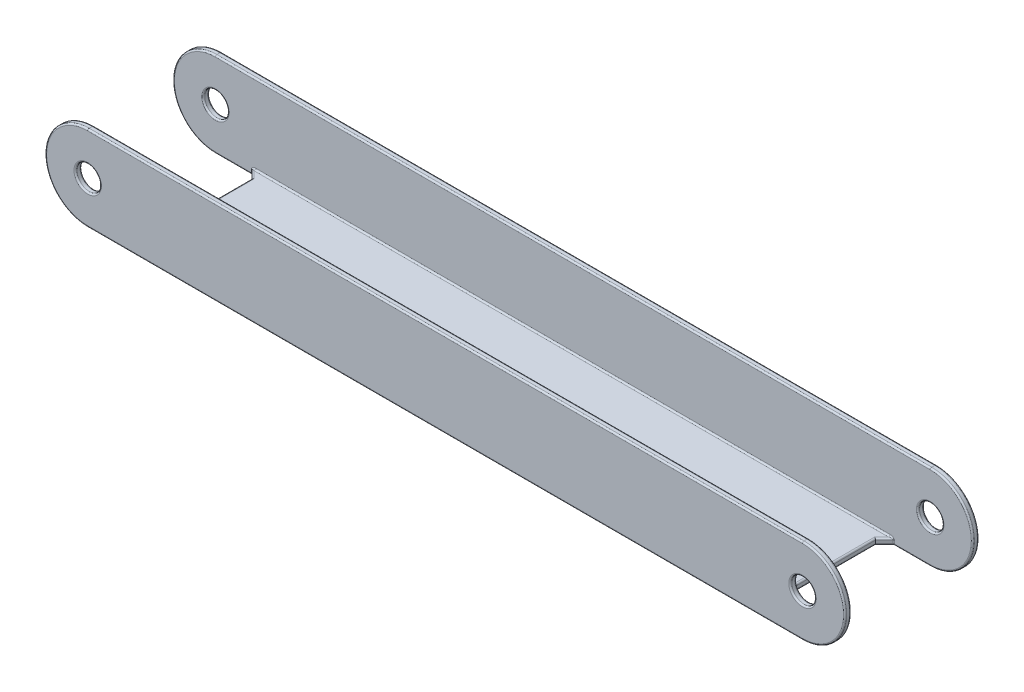
SolidWorks part; units mm, degrees
material "1023 Carbon Steel Sheet (SS)"
ref_plane "Front Plane" through (0, 0, 0) normal (0, 0, 1) x (1, 0, 0)
ref_plane "Top Plane" through (0, 0, 0) normal (0, 1, 0) x (1, 0, 0)
ref_plane "Right Plane" through (0, 0, 0) normal (1, 0, 0) x (0, 0, -1)
sketch "Sketch1" plane through (0, 0, 0) normal (0, 1, 0) x (1, 0, 0)
  line L0 (-125, 20) -> (125, 20)
  line L1 (-250, 0) -> (250, 0) construction
  line L2 (-125, -20) -> (125, -20)
  line L3 (125, -20) -> (125, 20)
  line L4 (-125, -20) -> (-125, 20)
  point P7 (0, 20)
  point P8 (0, -20)
  dimension "D1" = 40
  dimension "D2" = 250
  dimension "D3" = 500
extrude "Boss-Extrude1" add sketch "Sketch1" along normal blind 2
sketch "Sketch2" plane through (0, 0, 0) normal (0, 0, 1) x (1, 0, 0)
  line L0 (-125, 0) -> (125, 0) construction
  line L4 (-117.5, 0) -> (117.5, 0)
  line L5 (117.5, 28) -> (-117.5, 28)
  arc A0 (117.5, 0) -> (117.5, 28) centre (117.5, 14) ccw
  arc A1 (-117.5, 0) -> (-117.5, 28) centre (-117.5, 14) cw
  circle A2 centre (-117.5, 14) radius 4
  circle A3 centre (117.5, 14) radius 4
  dimension "D2" = 8
  dimension "D3" = 8
  dimension "D1" = 235
  dimension "D4" = 14
  dimension "D5" = 117.5
extrude "Boss-Extrude2" add sketch "Sketch2" along normal blind 2 from offset 20
mirror "Mirror1" about plane through (0, 0, 0) normal (0, 0, 1) of "Boss-Extrude2"
sketch "Sketch3" plane through (0, 2, 0) normal (0, 1, 0) x (1, 0, 0)
  line L0 (124.7111, 20) -> (-124.7111, 20) construction
  line L1 (102.5, 20) -> (183.801, 20)
  line L2 (102.5, 20) -> (102.5, -20)
  line L3 (102.5, -20) -> (183.801, -20)
  line L4 (183.801, 20) -> (183.801, -20)
  line L5 (-124.7111, -20) -> (124.7111, -20) construction
  line L6 (117.5, 22) -> (117.5, 20) construction
  dimension "D1" = 15
extrude "Cut-Extrude1" cut sketch "Sketch3" against normal through all
mirror "Mirror2" about plane through (0, 0, 0) normal (1, 0, 0) of "Cut-Extrude1"
chamfer "Chamfer1" distance 3 angle 45 4 edges at (-102.5, 1, -20) (-102.5, 1, 20) (102.5, 1, 20) (102.5, 1, -20)
fillet "Fillet1" radius 0.5 44 edges at (104, 0, 18.5) (102.5, 0, 0) (104, 0, -18.5) (-104, 0, -18.5) (-102.5, 0, 0) (-104, 0, 18.5) (0, 28, -22) (0, 0, -22) (131.5, 14, -22) (-131.5, 14, -22) (-113.5, 14, -22) (121.5, 14, -22) (-105.5, 1, -20) (-111.5, 0, -20) (-131.5, 14, -20) (0, 28, -20) (131.5, 14, -20) (111.5, 0, -20) (105.5, 1, -20) (121.5, 14, -20) (-113.5, 14, -20) (131.5, 14, 20) (0, 28, 20) (-131.5, 14, 20) (-111.5, 0, 20) (-105.5, 1, 20) (105.5, 1, 20) (111.5, 0, 20) (-113.5, 14, 20) (121.5, 14, 20) (104, 2, -18.5) (102.5, 2, 0) (104, 2, 18.5) (0, 2, 20) (-104, 2, 18.5) (-102.5, 2, 0) (-104, 2, -18.5) (0, 2, -20) (121.5, 14, 22) (-113.5, 14, 22) (0, 28, 22) (131.5, 14, 22) (0, 0, 22) (-131.5, 14, 22)
